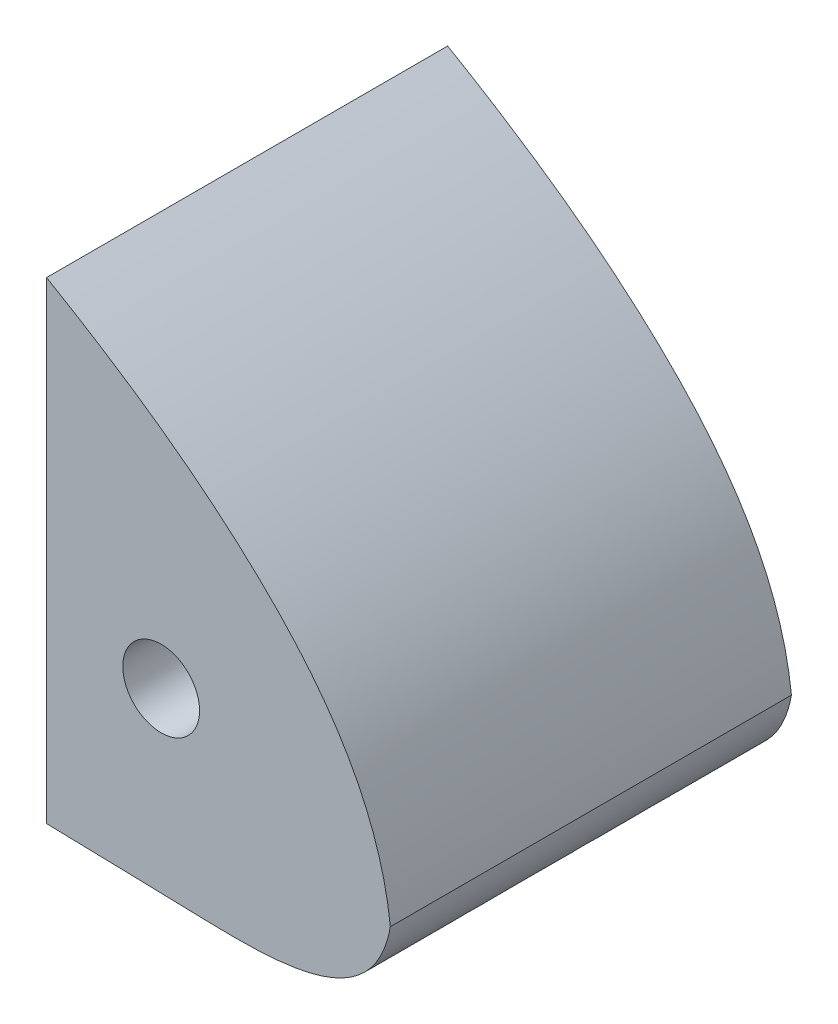
SolidWorks part; units mm, degrees
ref_plane "Front Plane" through (0, 0, 0) normal (0, 0, 1) x (1, 0, 0)
ref_plane "Top Plane" through (0, 0, 0) normal (0, 1, 0) x (1, 0, 0)
ref_plane "Right Plane" through (0, 0, 0) normal (1, 0, 0) x (0, 0, -1)
sketch "Sketch1" plane through (0, 0, 0) normal (0, 0, 1) x (1, 0, 0)
  line L0 (-66.007, 14.9523) -> (-66.007, -5.6347)
  circle A0 centre (63.517, -7.2283) radius 2.127
  circle A1 centre (-25.383, 13.0917) radius 2.127
  spline S0 degree 3 poles (76.217, -12.3083) (75.607, -6.7666) (69.7043, 1.1384) (56.4222, 10.2644) (36.9761, 19.3708) (8.7417, 24.8154) (-27.4552, 23.5667) (-52.3876, 18.1036) (-66.007, 14.9523) knots 0 0 0 0 0.086587 0.161737 0.268322 0.445157 0.638029 0.872371 0.872371 0.872371 0.872371
  spline S1 degree 3 poles (-66.007, -5.6347) (-44.594, -5.5392) (-13.013, -6.7241) (26.1367, -12.7509) (48.7653, -16.9008) (64.6834, -16.9691) (75.2906, -17.5225) (76.217, -12.3083) knots 0.133251 0.133251 0.133251 0.133251 0.51733 0.696667 0.84941 0.91952 1 1 1 1
extrude "Boss-Extrude1" add sketch "Sketch1" along normal blind 22.225
sketch "Sketch2" plane through (0, 0, 22.225) normal (0, 0, 1) x (1, 0, 0)
  line L0 (-66.007, 14.9523) -> (-66.007, -5.6347) construction
  line L1 (-77.1256, 30.6925) -> (57.167, 30.6925)
  line L2 (-77.1256, 30.6925) -> (-77.1256, -22.6703)
  line L3 (-77.1256, -22.6703) -> (57.167, -22.6703)
  line L4 (57.167, 30.6925) -> (57.167, -22.6703)
  dimension "D1" = 11.1187
  dimension "D2" = 19.05
extrude "Cut-Extrude1" cut sketch "Sketch2" against normal blind 28.956
